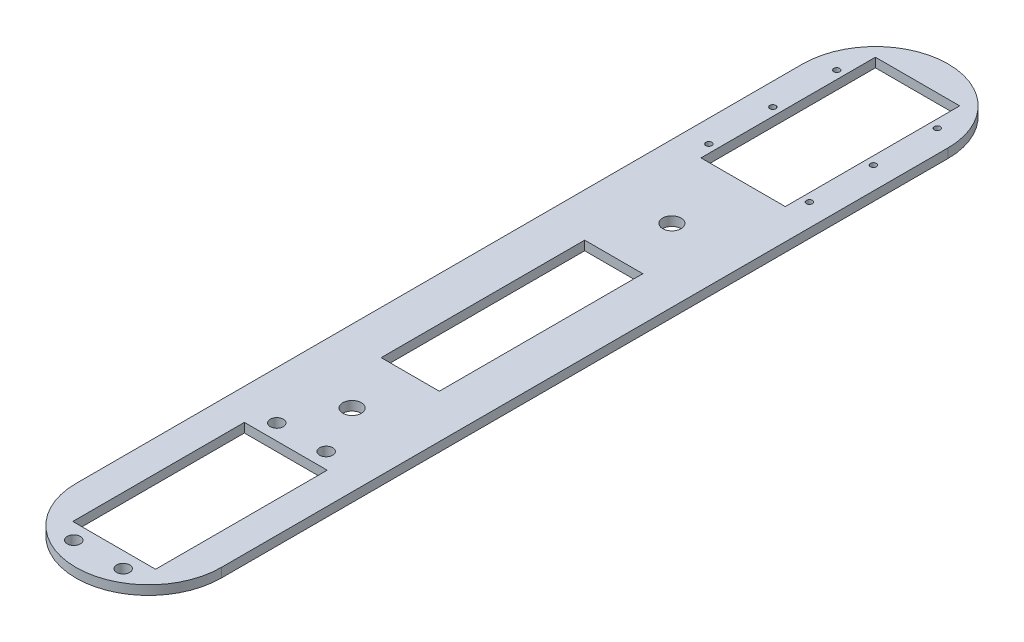
SolidWorks part; units mm, degrees
ref_plane "Front" through (0, 0, 0) normal (0, 0, 1) x (1, 0, 0)
ref_plane "Top" through (0, 0, 0) normal (0, 1, 0) x (1, 0, 0)
ref_plane "Right" through (0, 0, 0) normal (1, 0, 0) x (0, 0, -1)
sketch "Sketch2" plane through (0, 0, 0) normal (0, 1, 0) x (1, 0, 0)
  line L1 (0, 0) -> (50, 0)
  line L2 (0, 0) -> (0, -300)
  line L3 (0, -300) -> (50, -300)
  line L4 (50, 0) -> (50, -300)
  dimension "D1" = 300
  dimension "D2" = 50
extrude "Boss-Extrude1" add sketch "Sketch2" along normal blind 3.175
sketch "Sketch3" plane through (0, 3.175, 0) normal (0, 1, 0) x (1, 0, 0)
  line L0 (25, 0) -> (25, -300) construction
  line L1 (50, 0) -> (0, 0) construction
  line L2 (0, -300) -> (50, -300) construction
  line L3 (0, -150) -> (50, -150) construction
  line L4 (0, 0) -> (0, -300) construction
  line L5 (50, -300) -> (50, 0) construction
  line L6 (39.24, -257.325) -> (10.76, -257.325) construction
  line L7 (10.5, -10.5) -> (39.5, -10.5)
  line L8 (10.5, -10.5) -> (10.5, -70.5)
  line L9 (10.5, -70.5) -> (39.5, -70.5)
  line L10 (39.5, -10.5) -> (39.5, -70.5)
  line L11 (10.76, -227.81) -> (39.24, -227.81)
  line L12 (10.76, -227.81) -> (10.76, -286.84)
  line L13 (10.76, -286.84) -> (39.24, -286.84)
  line L14 (39.24, -227.81) -> (39.24, -286.84)
  circle A0 centre (7.7, -21) radius 1.025
  circle A1 centre (7.7, -43) radius 1.025
  circle A2 centre (7.7, -65) radius 1.025
  circle A3 centre (42.3, -65) radius 1.025
  circle A4 centre (42.3, -43) radius 1.025
  circle A5 centre (42.3, -21) radius 1.025
  circle A6 centre (16.5, -292.24) radius 2.25
  circle A7 centre (33.5, -292.24) radius 2.25
  circle A8 centre (16.5, -222.41) radius 2.25
  circle A9 centre (33.5, -222.41) radius 2.25
  dimension "D4" = 2.05
  dimension "D5" = 22
  dimension "D6" = 22
  dimension "D7" = 5.5
  dimension "D8" = 2.8
  dimension "D12" = 4.5
  dimension "D13" = 5.4
  dimension "D14" = 8.5
  dimension "D1" = 60
  dimension "D2" = 10.5
  dimension "D3" = 29
  dimension "D9" = 28.48
  dimension "D10" = 59.03
  dimension "D11" = 13.16
extrude "Cut-Extrude1" cut sketch "Sketch3" against normal blind 6.35
sketch "Sketch4" plane through (0, 3.175, 0) normal (0, 1, 0) x (1, 0, 0)
  line L0 (0, -25) -> (0, 0)
  line L1 (0, 0) -> (50, 0)
  line L2 (50, 0) -> (50, -25)
  line L3 (0, -275) -> (0, -300)
  line L4 (0, -300) -> (50, -300)
  line L5 (50, -300) -> (50, -275)
  circle A0 centre (25, -25) radius 25
  circle A1 centre (25, -275) radius 25
  line M19 (0, 0) -> (0, -300)
  line M20 (0, -300) -> (50, -300)
  line M21 (50, -300) -> (50, 0)
  line M22 (50, 0) -> (0, 0)
extrude "Cut-Extrude2" cut sketch "Sketch4" against normal blind 6.35 contours A0 L1 M19 | A0 M21 M22 | A1 M19 M20 | A1 L4 M21 region at (5.5842, 3.175, 5.5842) region at (44.4158, 3.175, 5.5842) region at (5.5842, 3.175, 294.4158) region at (44.4158, 3.175, 294.4158)
sketch "Sketch5" plane through (0, 0, 0) normal (0, -1, 0) x (1, 0, 0)
  line L0 (25, 300) -> (25, 0) construction
  line L1 (0, 150) -> (50, 150) construction
  line L2 (0, 25) -> (0, 275) construction
  line L3 (50, 275) -> (50, 25) construction
  line L5 (15, 185) -> (35, 185)
  line L6 (15, 185) -> (15, 115)
  line L7 (15, 115) -> (35, 115)
  line L8 (35, 185) -> (35, 115)
  arc A0 (50, 275) -> (0, 275) centre (25, 275) ccw construction
  arc A1 (0, 25) -> (50, 25) centre (25, 25) ccw construction
  circle A2 centre (25, 205) radius 3.175
  circle A3 centre (25, 95) radius 3.175
  dimension "D3" = 6.35
  dimension "D4" = 55
  dimension "D1" = 20
  dimension "D2" = 70
extrude "Cut-Extrude3" cut sketch "Sketch5" against normal blind 6.35
